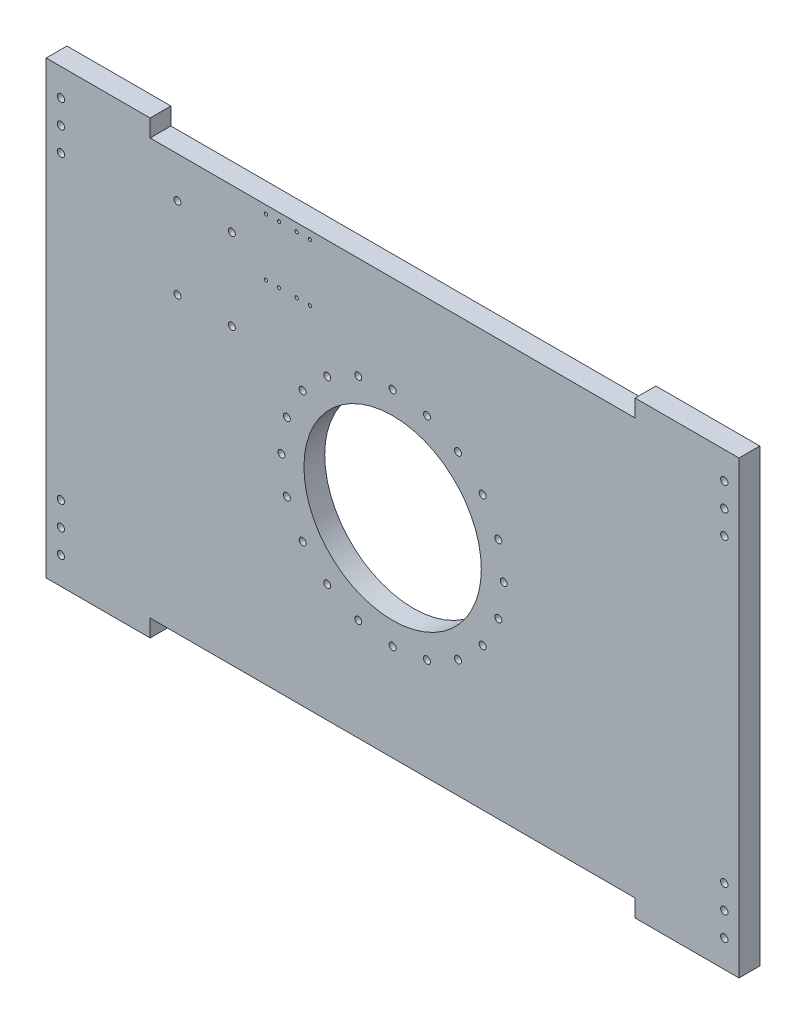
SolidWorks part; units mm, degrees
material "ASTM A36 Acier"
ref_plane "Plan de face" through (0, 0, 0) normal (0, 0, 1) x (1, 0, 0)
ref_plane "Plan de dessus" through (0, 0, 0) normal (0, 1, 0) x (1, 0, 0)
ref_plane "Plan de droite" through (0, 0, 0) normal (1, 0, 0) x (0, 0, -1)
sketch "Esquisse1" plane through (0, 0, 0) normal (0, 0, 1) x (1, 0, 0)
  line L0 (-1000, 1250) -> (-700, 1250)
  line L1 (-700, 1250) -> (-700, 1200)
  line L2 (-700, 1200) -> (700, 1200)
  line L3 (700, 1200) -> (700, 1250)
  line L4 (700, 1250) -> (1000, 1250)
  line L5 (1000, 1250) -> (1000, -50)
  line L6 (1000, -50) -> (700, -50)
  line L7 (700, -50) -> (700, 0)
  line L8 (700, 0) -> (-700, 0)
  line L9 (-700, 0) -> (-700, -50)
  line L10 (-700, -50) -> (-1000, -50)
  line L11 (-1000, -50) -> (-1000, 1250)
  point P15 (0, 0)
  dimension "D1" = 2000
  dimension "D2" = 50
  dimension "D4" = 300
  dimension "D5" = 300
  dimension "D6" = 300
  dimension "D7" = 300
  dimension "D8" = 1200
  dimension "D9" = 50
  dimension "D10" = 1400
extrude "Boss.-Extru.1" add sketch "Esquisse1" along normal blind 60
sketch "Esquisse2" plane through (0, 0, 60) normal (0, 0, 1) x (1, 0, 0)
  line L0 (700, -50) -> (1000, -50) construction
  circle A0 centre (0, 600) radius 256
  dimension "D1" = 512
  dimension "D2" = 650
extrude "Enlèv. mat.-Extru.1" cut sketch "Esquisse2" against normal through all
sketch "Esquisse4" plane through (0, 0, 0) normal (1, 0, 0) x (0, 0, -1)
  line L0 (0, 600) -> (1429.3387, 600) construction
  dimension "D1" = 600
sketch "Esquisse5" plane through (0, 0, 0) normal (0, 0, 1) x (1, 0, 0)
  circle A0 centre (0, 921) radius 10
  circle A1 centre (0, 600) radius 256 construction
  dimension "D1" = 20
  dimension "D2" = 321
extrude "Enlèv. mat.-Extru.3" cut sketch "Esquisse5" along normal through all
pattern_circular "Répétition circulaire1" count 20 every 18 about axis through (0, 600, 0) along (0, 0, -1) of "Enlèv. mat.-Extru.3"
ref_plane "Plan1" through (0, 0, 0) normal (0, 0, -1) x (-1, 0, 0)
sketch "Esquisse6" plane through (0, 0, 0) normal (0, 0, -1) x (-1, 0, 0)
  line L0 (1000, -50) -> (1000, 1250) construction
  line L1 (-1000, -50) -> (-1000, 1250) construction
  line L3 (0, 1100) -> (0, 0) construction
  line L5 (-700, -50) -> (-1000, -50) construction
  line L6 (994.9902, 600) -> (-1002.7622, 600) construction
  line L8 (700, 1200) -> (-700, 1200) construction
  circle A1 centre (-957.5, 28.75) radius 10.5
  circle A8 centre (-957.5, 1171.25) radius 10.5
  circle A9 centre (957.5, 1171.25) radius 10.5
  circle A14 centre (957.5, 28.75) radius 10.5
  circle A15 centre (-957.5, 97.5) radius 10.5
  circle A16 centre (-957.5, 166.25) radius 10.5
  circle A17 centre (-957.5, 1033.75) radius 10.5
  circle A18 centre (-957.5, 1102.5) radius 10.5
  circle A19 centre (957.5, 97.5) radius 10.5
  circle A20 centre (957.5, 166.25) radius 10.5
  circle A21 centre (957.5, 1102.5) radius 10.5
  circle A22 centre (957.5, 1033.75) radius 10.5
  point P5 (1000, 600)
  point P14 (0, 1200)
  dimension "D2" = 3
  dimension "D9" = 78.75
  dimension "21" = 21
  dimension "D10" = 42.5
extrude "Enlèv. mat.-Extru.4" cut sketch "Esquisse6" against normal through all
ref_plane "Plan2" through (-1000, -50, 60) normal (0, -1, 0) x (-1, 0, 0)
ref_plane "Plan7" through (-644.2059, 810, 60) normal (1, 0, 0) x (0, 0, -1)
sketch "Esquisse11" plane through (0, 0, 0) normal (0, 0, -1) x (-1, 0, 0)
  circle A0 centre (464, 847.5) radius 10
  circle A1 centre (621, 847.5) radius 10
  circle A2 centre (621, 1082.5) radius 10
  circle A3 centre (464, 1082.5) radius 10
extrude "Enlèv. mat.-Extru.5" cut sketch "Esquisse11" against normal blind 100 and the other way through all
sketch "Esquisse12" plane through (0, 0, 0) normal (0, 0, -1) x (-1, 0, 0)
  circle A0 centre (238.7481, 1177.1251) radius 4.7625
  circle A1 centre (327.6481, 1177.1251) radius 4.7625
  circle A2 centre (238.7481, 1012.0251) radius 4.7625
  circle A3 centre (276.8481, 1012.0251) radius 4.7625
  circle A4 centre (327.6481, 1012.0251) radius 4.7641
  circle A5 centre (365.7481, 1012.0251) radius 4.7625
  circle A6 centre (365.7481, 1177.1251) radius 4.7625
  circle A7 centre (276.8481, 1177.1251) radius 4.7625
extrude "Enlèv. mat.-Extru.6" cut sketch "Esquisse12" against normal blind 100
